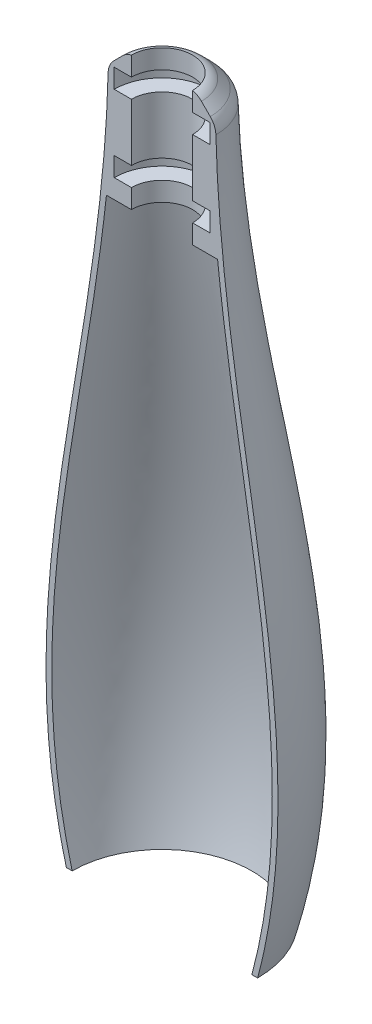
SolidWorks part; units mm, degrees
material "ABS"
ref_plane "Alzado" through (0, 0, 0) normal (0, 0, 1) x (1, 0, 0)
ref_plane "Planta" through (0, 0, 0) normal (0, 1, 0) x (1, 0, 0)
ref_plane "Vista lateral" through (0, 0, 0) normal (1, 0, 0) x (0, 0, -1)
sketch "Croquis1" plane through (0, 0, 0) normal (0, 0, 1) x (1, 0, 0)
  line L0 (0, 50) -> (0, -350) construction
  line L1 (-15, -35) -> (15, -35) construction
  line L2 (-15, -35) -> (-15, 35) construction
  line L3 (-15, 35) -> (15, 35) construction
  line L4 (15, -35) -> (15, 35) construction
  line L5 (-15, -35) -> (15, 35) construction
  line L6 (-15, 35) -> (15, -35) construction
  line L7 (-25, 15) -> (25, 15) construction
  line L8 (-25, 15) -> (-25, 25) construction
  line L9 (-25, 25) -> (25, 25) construction
  line L10 (25, 15) -> (25, 25) construction
  line L11 (-25, 15) -> (25, 25) construction
  line L12 (-25, 25) -> (25, 15) construction
  line L13 (-25, -25) -> (25, -25) construction
  line L14 (-25, -25) -> (-25, -15) construction
  line L15 (-25, -15) -> (25, -15) construction
  line L16 (25, -25) -> (25, -15) construction
  line L17 (-25, -25) -> (25, -15) construction
  line L18 (-25, -15) -> (25, -25) construction
  line L19 (-28, 35) -> (-16, 35)
  line L20 (-16, 35) -> (-16, 25)
  line L21 (-16, 25) -> (-25, 25)
  line L22 (-25, 15) -> (-16, 15)
  line L23 (-16, 15) -> (-16, -15)
  line L24 (-25, 25) -> (-25, 15)
  line L25 (-25, -15) -> (-25, -25)
  line L26 (-50, -350) -> (-47, -350)
  line L27 (0, -350) -> (-50, -350) construction
  line L28 (-50, -350) -> (-47, -350) construction
  line L29 (-25, -15) -> (-25, -25)
  line L30 (-16, -15) -> (-25, -15)
  line L31 (-25, -15) -> (-25.1652, -14.7279)
  line L32 (-25, -25) -> (-16, -25)
  line L33 (-16, -25) -> (-16, -35)
  line L34 (-16, -35) -> (-29.067, -35)
  line L37 (-15, -25) -> (-15, -35)
  line L39 (-25, 25) -> (-25, 15)
  spline S0 degree 3 poles (-28, 35) (-28, -105.9083) (-83.2693, -225.8373) (-50, -350) knots 0 0 0 0 1 1 1 1
  spline S1 degree 3 poles (-47, -350) (-74.6274, -246.8932) (-41.1993, -146.706) (-29.067, -35) knots 0 0 0 0 0.830417 0.830417 0.830417 0.830417
  point P0 (0, 0)
  point P6 (0, 20)
  point P11 (0, -20)
  dimension "D1" = 400
  dimension "D2" = 50
  dimension "D3" = 50
  dimension "D4" = 13
  dimension "D5" = 12
  dimension "D6" = 3
revolve "Revolución1" add sketch "Croquis1" angle 360 about L0 region at (-22, 31.1242, 0)
sketch "Croquis2" plane through (0, 0, 0) normal (1, 0, 0) x (0, 0, -1)
  line L0 (-50, -350) -> (50, -350) construction
  line L1 (0, -350) -> (-77.2595, -350)
  line L2 (0, -350) -> (0, 41.1672)
  line L3 (0, 41.1672) -> (-77.2595, 41.1672)
  line L4 (-77.2595, -350) -> (-77.2595, 41.1672)
extrude "Cortar-Extruir1" cut sketch "Croquis2" against normal blind 70 and the other way blind 70
chamfer "Chaflán1" distance 10 angle 45 1 edges at (0, 35, -28)
fillet "Redondeo1" radius 10 2 edges at (0, 24.9068, -28.0932) (0, 35, -18)
